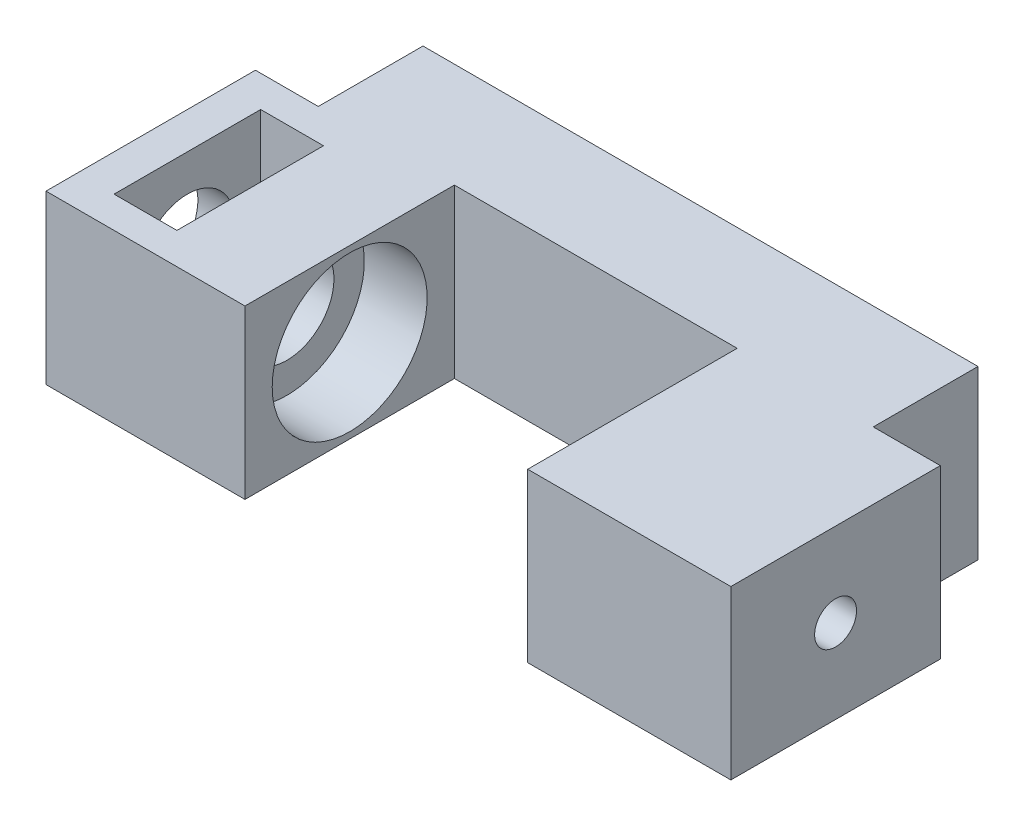
SolidWorks part; units mm, degrees
material "ABS"
ref_plane "Plan de face" through (0, 0, 0) normal (0, 0, 1) x (1, 0, 0)
ref_plane "Plan de dessus" through (0, 0, 0) normal (0, 1, 0) x (1, 0, 0)
ref_plane "Plan de droite" through (0, 0, 0) normal (1, 0, 0) x (0, 0, -1)
sketch "Length" plane through (0, 0, 0) normal (0, 1, 0) x (1, 0, 0)
  line L0 (0, 0) -> (0, 117) construction
  dimension "D1" = 117
sketch "Length2" plane through (0, 0, 0) normal (1, 0, 0) x (0, 0, -1)
  line L0 (100, 0) -> (100, 40) construction
  line L1 (0, 0) -> (117, 0) construction
  dimension "D1" = 40
  dimension "D2" = 100
sketch3d "TopPlane"
sketch "Esquisse17" plane through (0, 40, 0) normal (0, -1, 0) x (-1, 0, 0)
  line L0 (13.25, 105) -> (13.25, 95)
  line L1 (13.25, 95) -> (6.75, 95)
  line L2 (6.75, 95) -> (6.75, 105)
  line L3 (6.75, 105) -> (-6.75, 105)
  line L4 (-6.75, 105) -> (-6.75, 95)
  line L5 (-6.75, 95) -> (-13.25, 95)
  line L6 (-13.25, 95) -> (-13.25, 105)
  line L7 (-13.25, 105) -> (-13.25, 110)
  line L8 (-13.25, 110) -> (13.25, 110)
  line L9 (13.25, 110) -> (13.25, 105)
  line L10 (0, 0) -> (0, 117) construction
  line L11 (0, 100) -> (13.25, 100) construction
  line L12 (13.25, 105) -> (6.75, 105) construction
  line L13 (-6.75, 105) -> (-13.25, 105) construction
  line L14 (-10, 105) -> (-10, 95) construction
  line L15 (10, 105) -> (10, 95) construction
  point P12 (0, 105)
  dimension "D1" = 6.5
  dimension "D2" = 5
  dimension "D3" = 20
  dimension "D4" = 10
  dimension "D5" = 5
extrude "Shape" add sketch "Esquisse17" along normal blind 4 and the other way blind 4 separate body
sketch "Esquisse19" plane through (-13.25, 0, 0) normal (-1, 0, 0) x (0, 0, 1)
  circle A0 centre (-100, 40) radius 2.25
  dimension "D1" = 4.5
extrude "HoleAxe_motor" cut sketch "Esquisse19" against normal blind 13
sketch "Esquisse20" plane through (6.75, 0, 0) normal (-1, 0, 0) x (0, 0, 1)
  circle A0 centre (-100, 40) radius 3.7
  dimension "D1" = 7.4
extrude "HoleBearing_motor" cut sketch "Esquisse20" against normal blind 3
mirror "Symétrie3" about plane through (0, 0, 0) normal (1, 0, 0) of "HoleBearing_motor"
sketch "Esquisse21" plane through (9.75, 0, 0) normal (-1, 0, 0) x (0, 0, 1)
  circle A0 centre (-100, 40) radius 2.2
  circle A1 centre (-100, 40) radius 3.7 construction
  dimension "D1" = 1.5
extrude "entretoiseBearing_motor" cut sketch "Esquisse21" against normal blind 1
sketch "Esquisse22" plane through (-13.25, 0, 0) normal (-1, 0, 0) x (0, 0, 1)
  line L0 (-95, 36) -> (-110, 36) construction
  line L1 (-95, 44) -> (-105, 44)
  line L2 (-95, 44) -> (-95, 36)
  line L3 (-95, 36) -> (-105, 36)
  line L4 (-105, 44) -> (-105, 36)
  circle A0 centre (-100, 40) radius 2.25
  circle A1 centre (-100, 40) radius 2.25 construction
extrude "Ext_motor" add sketch "Esquisse22" along normal blind 3
sketch "Esquisse23" plane through (0, 44, 0) normal (0, 1, 0) x (1, 0, 0)
  line L0 (-13.25, 105) -> (-6.75, 105) construction
  line L1 (-9.75, 95) -> (-9.75, 105) construction
  line L2 (-6.75, 95) -> (-16.25, 95) construction
  line L3 (-9.75, 100) -> (-16.25, 100) construction
  line L4 (-16.25, 95) -> (-16.25, 105) construction
  line L5 (-9.75, 96.3) -> (-9.75, 103.7) construction
  line L7 (-14.5, 96.5) -> (-11.5, 96.5)
  line L8 (-14.5, 96.5) -> (-14.5, 103.5)
  line L9 (-14.5, 103.5) -> (-11.5, 103.5)
  line L10 (-11.5, 96.5) -> (-11.5, 103.5)
  line L11 (-14.5, 96.5) -> (-11.5, 103.5) construction
  line L12 (-14.5, 103.5) -> (-11.5, 96.5) construction
  point P14 (-13, 100)
  dimension "D1" = 3
  dimension "D2" = 7
extrude "HoleScrewLess_motor" cut sketch "Esquisse23" against normal blind 10
sketch "Esquisse24" plane through (13.25, 0, 0) normal (1, 0, 0) x (0, 0, -1)
  line L5 (105, 44) -> (105, 36) construction
  line L6 (105, 36) -> (95, 36)
  line L7 (105, 36) -> (105, 44)
  line L8 (105, 44) -> (95, 44)
  line L9 (95, 36) -> (95, 44)
  line L10 (105, 36) -> (95, 44) construction
  line L11 (105, 44) -> (95, 36) construction
  point P0 (100, 40)
extrude "Boss.-Extru.1" add sketch "Esquisse24" along normal blind 3.2
sketch "Esquisse25" plane through (10.75, 0, 0) normal (-1, 0, 0) x (0, 0, 1)
  circle A0 centre (-100, 40) radius 1
  dimension "D1" = 2
extrude "Remove helper" cut sketch "Esquisse25" against normal blind 10
equation "\"entretoiseBearing\"= 1.5mm"
equation "\"length_tibia\"= 206mm"
equation "\"length_femur\"= 117mm"
equation "\"length_coxa\"= 27mm"
equation "\"height\"= 40mm"
equation "\"width\"= 100mm"
equation "\"lever\"= 40mm"
equation "\"depthMagnet\"= 1mm"
equation "\"D1@Length\"=\"length_femur\""
equation "\"D1@Length2\"=\"height\""
equation "\"D1@Esquisse19\"=\"entretoiseBearing\"+3"
equation "\"D1@Esquisse21\"=\"entretoiseBearing\""
equation "\"D2@Length2\"=\"width\""
equation "\"D1@Ref\" = \"length_femur\""
equation "\"errorFlat\"= 0.20mm"
equation "\"errorCircle\"= 0.40mm"
equation "\"cuticule\"=1.5mm"
equation "\"D1@Esquisse20\"=\"errorCircle\"+7"
equation "\"D1@Boss.-Extru.1\"=\"errorFlat\"+3"
